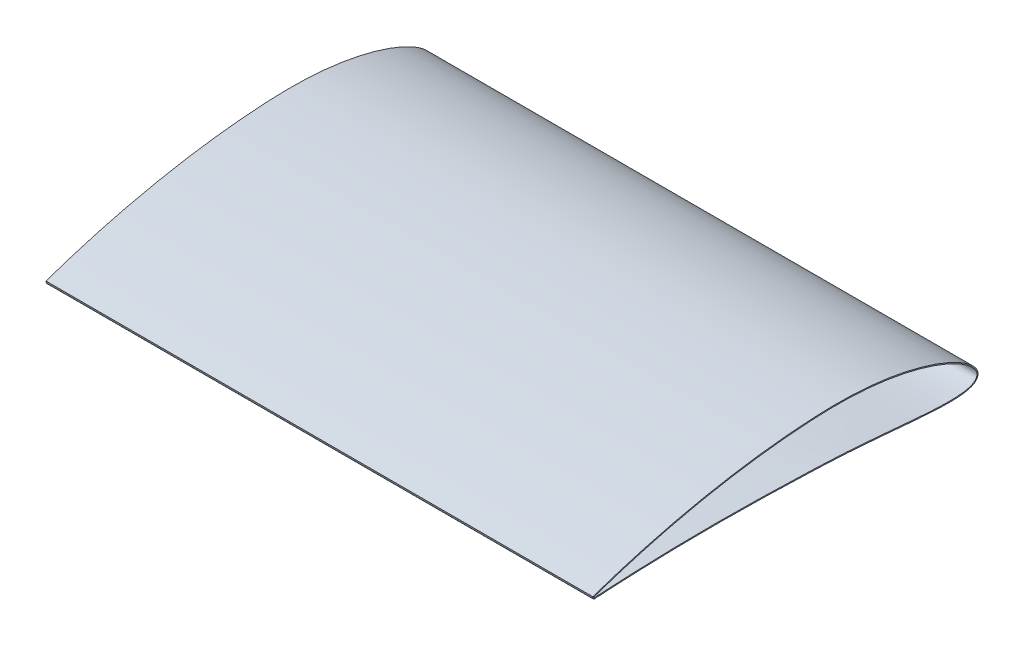
SolidWorks part; units mm, degrees
material "E-Glass Fiber"
ref_plane "Front Plane" through (0, 0, 0) normal (0, 0, 1) x (1, 0, 0)
ref_plane "Top Plane" through (0, 0, 0) normal (0, 1, 0) x (1, 0, 0)
ref_plane "Right Plane" through (0, 0, 0) normal (1, 0, 0) x (0, 0, -1)
curve "Curve1"
  spline degree 3 poles (0, 0.0012, 1.0003) (0, 0.0015, 0.9994) (0, 0.0028, 0.9958) (0, 0.0055, 0.9879) (0, 0.0099, 0.9747) (0, 0.0159, 0.9565) (0, 0.0233, 0.9333) (0, 0.0318, 0.9054) (0, 0.0411, 0.8731) (0, 0.051, 0.8366) (0, 0.0612, 0.7964) (0, 0.0713, 0.7528) (0, 0.0811, 0.7063) (0, 0.0903, 0.6574) (0, 0.0985, 0.6067) (0, 0.1057, 0.5546) (0, 0.1115, 0.5018) (0, 0.1158, 0.4488) (0, 0.1186, 0.3959) (0, 0.1189, 0.3436) (0, 0.1164, 0.2927) (0, 0.1112, 0.2442) (0, 0.1037, 0.1988) (0, 0.0942, 0.157) (0, 0.0831, 0.1194) (0, 0.0711, 0.0865) (0, 0.0584, 0.0585) (0, 0.0457, 0.0357) (0, 0.0334, 0.0184) (0, 0.0218, 0.0064) (0, 0.0108, -0.0005) (0, -0.0003, -0.0011) (0, -0.0092, 0.0055) (0, -0.0148, 0.017) (0, -0.0185, 0.0329) (0, -0.0204, 0.0533) (0, -0.0208, 0.0781) (0, -0.0198, 0.107) (0, -0.0176, 0.1398) (0, -0.0147, 0.176) (0, -0.0111, 0.2153) (0, -0.0074, 0.2574) (0, -0.0037, 0.3019) (0, -0.0005, 0.3484) (0, 0.002, 0.397) (0, 0.0037, 0.4471) (0, 0.0055, 0.4983) (0, 0.0069, 0.5496) (0, 0.0079, 0.6006) (0, 0.0085, 0.6505) (0, 0.0086, 0.699) (0, 0.0083, 0.7455) (0, 0.0076, 0.7894) (0, 0.0065, 0.8302) (0, 0.0053, 0.8675) (0, 0.0039, 0.9007) (0, 0.0027, 0.9296) (0, 0.0013, 0.9539) (0, 0.0006, 0.9727) (0, -0.0011, 0.9872) (0, 0, 0.9944) (0, -0.002, 0.9999) (0, -0.0005, 1) (0, 0, 1) knots 0 0 0 0 0.001372 0.005465 0.012235 0.021602 0.033461 0.047671 0.064081 0.082496 0.102719 0.124527 0.147676 0.171913 0.196978 0.222597 0.248497 0.274385 0.300041 0.32569 0.350525 0.37428 0.396711 0.417577 0.436654 0.453744 0.46868 0.481329 0.491631 0.499616 0.505546 0.510185 0.514824 0.520702 0.528516 0.538466 0.550543 0.564643 0.580638 0.598345 0.617584 0.638174 0.659922 0.682632 0.706121 0.730727 0.7557 0.780732 0.805564 0.829932 0.85357 0.876213 0.89761 0.917519 0.935698 0.951943 0.966047 0.97784 0.987174 0.993932 0.998018 0.999386 1 1 1 1
sketch "Sketch1" plane through (0, 0, 0) normal (1, 0, 0) x (0, 0, -1)
  line L0 (-354.7873, -0.0303) -> (-354.8762, 0.4104)
  line L1 (-354.7873, -0.0303) -> (0.8093, 1.5275) construction
  line L2 (0.8093, 1.5275) -> (0.7921, 5.4415) construction
  line L3 (-355.7813, -0.16) -> (-356.0294, 1.0708)
  spline S0 degree 1 poles (-356.0294, 1.0708) (-355.7813, -0.16) knots 0 0 1 1 construction
  spline S1 degree 3 poles (-354.8762, 0.4104) (-354.5599, 0.5194) (-353.2997, 0.9536) (-350.4787, 1.9271) (-345.801, 3.4978) (-336.0241, 6.7216) (-319.6545, 11.7989) (-300.5983, 17.1306) (-282.4229, 21.7243) (-261.1758, 26.6516) (-238.6223, 31.1455) (-208.7748, 36.0048) (-183.9617, 39.0905) (-158.9023, 41.1132) (-140.0967, 42.1114) (-121.5167, 42.2289) (-103.4222, 41.3211) (-86.1884, 39.4787) (-70.0435, 36.8105) (-55.1998, 33.4329) (-41.8434, 29.5109) (-30.1305, 25.2201) (-20.187, 20.7343) (-12.1072, 16.2263) (-5.9269, 11.8553) (-1.6792, 7.7165) (0.7658, 3.7968) (0.9875, -0.1483) (-1.3511, -3.3089) (-5.4508, -5.2881) (-11.0873, -6.5875) (-18.3491, -7.2685) (-27.1638, -7.4049) (-37.4471, -7.0538) (-49.0831, -6.3019) (-61.9524, -5.238) (-75.9299, -3.9839) (-96.4067, -2.1536) (-117.9372, -0.4584) (-140.4848, 0.6745) (-158.2965, 1.2867) (-176.4839, 1.9179) (-200.672, 2.5862) (-224.5411, 2.9791) (-247.8302, 3.0285) (-264.3373, 2.9074) (-279.9331, 2.6564) (-294.438, 2.2829) (-307.6819, 1.8521) (-319.5134, 1.3711) (-329.7674, 0.9129) (-338.3889, 0.4268) (-345.077, 0.1915) (-350.2276, -0.4064) (-352.7802, -0.0354) (-354.7446, -0.7581) (-354.7772, -0.2025) (-354.7873, -0.0303) knots 0 0 0 0 0.001372 0.005465 0.012235 0.021602 0.047671 0.082496 0.102719 0.124527 0.171913 0.196978 0.248497 0.274385 0.300041 0.32569 0.350525 0.37428 0.396711 0.417577 0.436654 0.453744 0.46868 0.481329 0.491631 0.499616 0.505546 0.510185 0.514824 0.520702 0.528516 0.538466 0.550543 0.564643 0.580638 0.598345 0.617584 0.638174 0.682632 0.706121 0.730727 0.7557 0.780732 0.829932 0.85357 0.876213 0.89761 0.917519 0.935698 0.951943 0.966047 0.97784 0.987174 0.993932 0.998018 0.999386 1 1 1 1
  spline S2 degree 3 poles (-356.0294, 1.0708) (-348.8068, 3.5591) (-334.3137, 8.3987) (-305.0227, 17.1398) (-267.9722, 26.5042) (-230.4397, 33.7217) (-200.1876, 38.1139) (-177.3993, 40.6676) (-154.5431, 42.4484) (-131.6073, 43.3755) (-108.6332, 42.7966) (-89.5704, 40.9369) (-74.434, 38.5689) (-63.1626, 36.3176) (-52.0007, 33.5569) (-40.9837, 30.2424) (-31.9663, 26.9597) (-24.8924, 23.9577) (-19.678, 21.4886) (-14.5784, 18.7674) (-9.6365, 15.7331) (-5.7201, 12.8485) (-2.8041, 10.2108) (-0.8097, 7.9993) (0.9536, 5.4706) (1.8267, 2.8505) (1.8287, 0.5804) (1.3439, -1.1087) (0.4339, -2.5446) (-1.1152, -4.1337) (-3.4092, -5.4544) (-6.2413, -6.4463) (-9.1163, -7.1407) (-12.9596, -7.769) (-17.7821, -8.1875) (-23.5483, -8.3615) (-29.3027, -8.3178) (-35.0455, -8.1273) (-40.7762, -7.8324) (-48.4067, -7.3387) (-57.9264, -6.5844) (-69.3333, -5.5826) (-80.7332, -4.5557) (-92.1313, -3.5515) (-107.3326, -2.2957) (-126.3437, -0.9632) (-145.3831, -0.1511) (-160.6352, 0.3667) (-175.8853, 0.8944) (-194.9456, 1.4407) (-217.8243, 1.8769) (-236.8904, 2.025) (-252.1434, 1.9977) (-263.5829, 1.9042) (-275.0214, 1.7404) (-286.4576, 1.4951) (-295.9876, 1.2274) (-303.6097, 0.9813) (-309.3259, 0.7769) (-315.0428, 0.5518) (-320.7576, 0.3113) (-326.4654, 0.0596) (-331.2293, -0.1801) (-335.0499, -0.3834) (-337.9104, -0.5288) (-340.7518, -0.6489) (-343.1033, -0.7582) (-345.0032, -0.8822) (-346.443, -1.005) (-347.9246, -1.1411) (-349.3933, -1.2404) (-350.6256, -1.2477) (-351.5127, -1.1926) (-352.1109, -1.176) (-352.6084, -1.2069) (-353.0416, -1.2775) (-353.3273, -1.3432) (-353.5861, -1.418) (-353.834, -1.4893) (-354.1253, -1.5551) (-354.4896, -1.5941) (-354.9528, -1.5235) (-355.3731, -1.2467) (-355.6868, -0.8168) (-355.7586, -0.4226) (-355.7748, -0.2607) (-355.7813, -0.16) knots -0.001196 -0.001196 -0.001196 -0.001196 0.030089 0.061374 0.123944 0.186514 0.217798 0.249083 0.280368 0.311653 0.342938 0.374223 0.389866 0.405508 0.421151 0.436793 0.452436 0.460257 0.468078 0.475899 0.483721 0.491542 0.495452 0.499363 0.503274 0.507184 0.50914 0.511095 0.51305 0.515005 0.518916 0.522827 0.526737 0.530648 0.538469 0.54629 0.554112 0.561933 0.569754 0.577575 0.593218 0.60886 0.624503 0.640145 0.655788 0.687073 0.718358 0.734 0.749643 0.780928 0.812212 0.843497 0.85914 0.874782 0.890425 0.906067 0.92171 0.929531 0.937352 0.945174 0.952995 0.960816 0.968637 0.972548 0.976458 0.980369 0.98428 0.986235 0.98819 0.990146 0.992101 0.994056 0.995034 0.996012 0.996989 0.997478 0.997967 0.998211 0.998456 0.9987 0.998945 0.999189 0.999311 0.999433 0.999678 0.999922 0.999922 0.999922 0.999922
  dimension "D1" = 355.6
  dimension "D2" = 1
extrude "Boss-Extrude1" add sketch "Sketch1" along normal blind 254 and the other way blind 254
